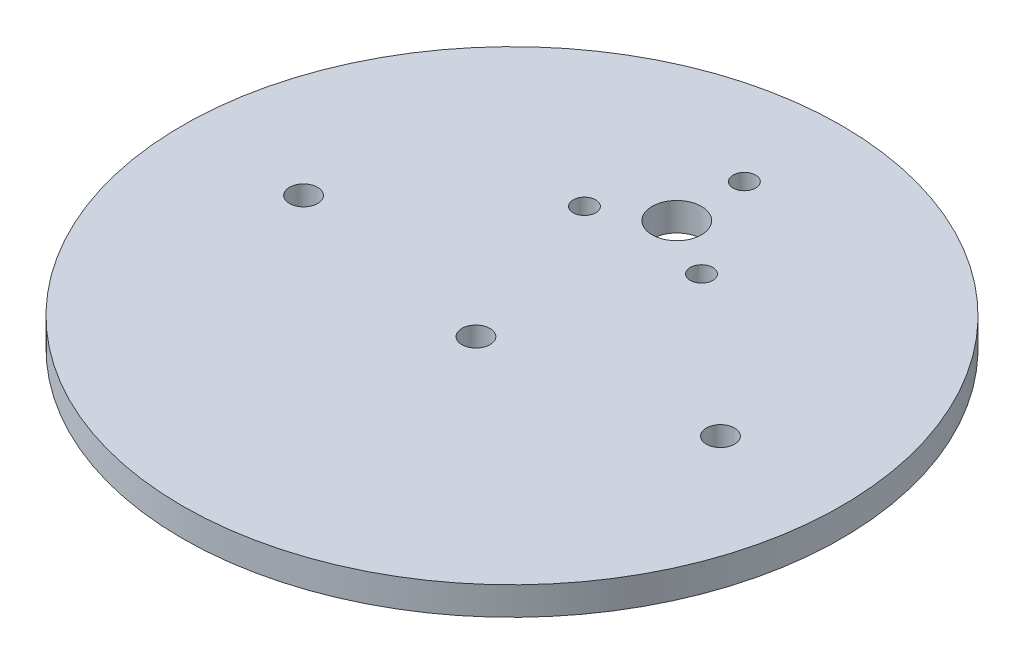
SolidWorks part; units mm, degrees
ref_plane "前视基准面" through (0, 0, 0) normal (0, 0, 1) x (1, 0, 0)
ref_plane "上视基准面" through (0, 0, 0) normal (0, 1, 0) x (1, 0, 0)
ref_plane "右视基准面" through (0, 0, 0) normal (1, 0, 0) x (0, 0, -1)
sketch "Sketch1" plane through (0, 0, 0) normal (0, 1, 0) x (1, 0, 0)
  circle A0 centre (0, 0) radius 74.295
  dimension "D1" = 148.59
extrude "Boss-Extrude1" add sketch "Sketch1" along normal blind 6.35
sketch "Sketch2" plane through (0, 6.35, 0) normal (0, 1, 0) x (1, 0, 0)
  line L0 (0, 74.295) -> (0, 0) construction
  circle A0 centre (0, 0) radius 74.295 construction
  circle A1 centre (0, 37.1475) radius 21.4376 construction
  circle A2 centre (0, 37.1475) radius 5.5626
  circle A3 centre (0, 52.3875) radius 2.54
  circle A4 centre (13.1982, 29.5275) radius 2.54
  circle A5 centre (-13.1982, 29.5275) radius 2.54
  point P16 (0, 37.1475)
  dimension "D1" = 42.8752
  dimension "D2" = 11.1252
  dimension "D4" = 5.08
  dimension "D3" = 15.24
  dimension "D5" = 3
extrude "CO2Ejec_Flange_Holes" cut sketch "Sketch2" against normal up to surface (6.35 mm away) up to face at (0, 0, 74.295)
sketch "Sketch3" plane through (0, 6.35, 0) normal (0, 1, 0) x (1, 0, 0)
  line L0 (-74.295, 0) -> (74.295, 0) construction
  line L1 (0, 74.295) -> (0, -74.295) construction
  circle A0 centre (0, 0) radius 74.295 construction
  circle A1 centre (0, -8.128) radius 3.175
  circle A2 centre (-46.99, 0) radius 3.175
  circle A3 centre (46.99, 0) radius 3.175
  point P19 (0, 0)
  dimension "D1" = 6.35
  dimension "D2" = 6.35
  dimension "D3" = 8.128
  dimension "D4" = 46.99
extrude "EyeboltsnRod_Holes" cut sketch "Sketch3" against normal up to surface (6.35 mm away) up to face at (0, 0, -49.8475)
